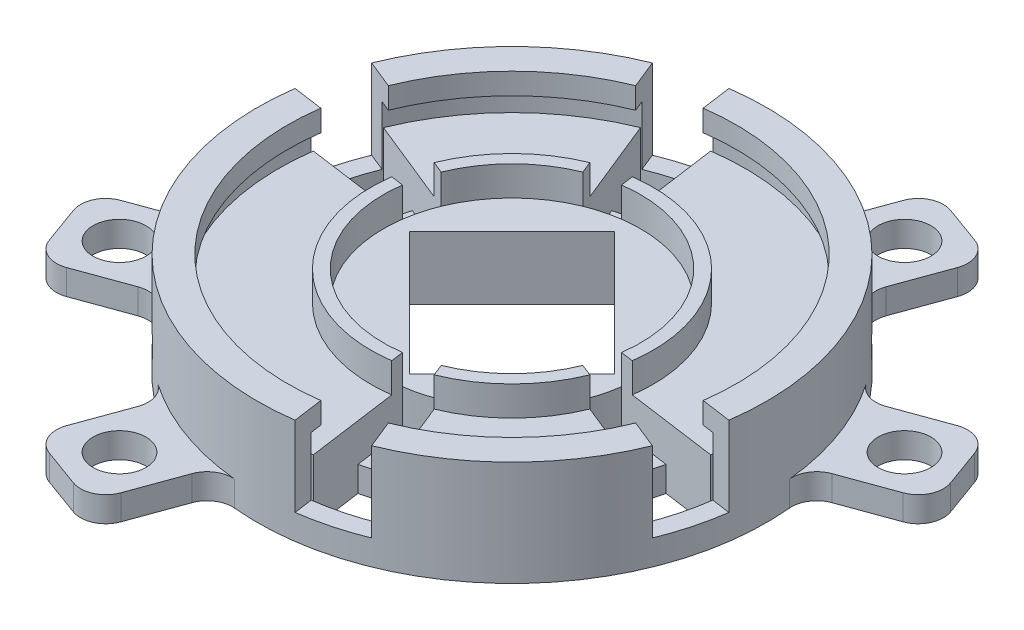
SolidWorks part; units mm, degrees
note: The reader was unsure of these and kept them because the rebuilt part matched: shared geometry of "Sketch1<4>".
other "outer_ring"
other "inner_ring" parameters "D1"=2.4937, "D6"=4.2, "D7"=4.2, "D8"=4.2, "D3"=2.6742, "D4"=3.0934, "D2"=7.9846, "D5"=6.2037
ref_plane "Front Plane" through (0, 0, 0) normal (0, 0, 1) x (1, 0, 0)
ref_plane "Top Plane" through (0, 0, 0) normal (0, 1, 0) x (1, 0, 0)
ref_plane "Right Plane" through (0, 0, 0) normal (1, 0, 0) x (0, 0, -1)
sketch "Sketch1" plane through (0, 0, 0) normal (0, 0, 1) x (1, 0, 0)
  line L4 (17.5401, 1.65) -> (17.5401, 3.34)
  line L5 (17.5401, 3.34) -> (19.9401, 3.34)
  line L6 (19.9401, 3.34) -> (19.9401, -5)
  line L7 (19.9401, -5) -> (-0.2599, -5)
  line L9 (10.9401, 0) -> (18.4401, 0)
  line L10 (16.9401, 3.15) -> (16.9401, 1.55) construction
  line L11 (10.9401, 0) -> (10.9401, 2.35)
  line L15 (-0.2599, 0) -> (-0.2599, -5)
  line L16 (18.2401, 0) -> (18.2401, 1.55) construction
  line L18 (9.9401, 2.35) -> (9.9401, 0)
  line L19 (18.4401, 0) -> (18.4401, 1.65)
  line L20 (9.9401, 0) -> (-0.2599, 0)
  line L21 (-18.7599, 1.55) -> (18.2401, 1.55) construction
  line L22 (-0.2599, -998.45) -> (-0.2599, 49001.55) construction
  line L23 (10.9401, -4) -> (10.9401, 0)
  line L24 (10.9401, -4) -> (-0.2599, -4)
  line L25 (18.4401, 0) -> (18.4401, -5)
  line L27 (10.9401, 2.35) -> (9.9401, 2.35)
  line L28 (9.2788, 3.15) -> (9.2788, 1.55) construction
  line L30 (18.4401, 1.65) -> (17.5401, 1.65)
  line L31 (18.2401, -5) -> (18.2401, 0)
  line L32 (-18.7599, 0) -> (18.2401, 0) construction
  line L33 (11.0901, 0) -> (11.0901, 1.55) construction
  point P24 (9.2788, 2.35)
  point P28 (-0.2599, 1.55)
  dimension "D1" = 5
  dimension "D2" = 0.6
  dimension "D3" = 1.69
  dimension "D4" = 0.2
  dimension "D5" = 1
  dimension "D6" = 0.1
  dimension "D7" = 0.7
  dimension "D8" = 4
  dimension "D9" = 1.5
  dimension "D10" = 0.15
revolve "Revolve1" add sketch "Sketch1" angle 360 about L22
revolve "Revolve3" add sketch "Sketch1<4>" angle 360 about L22
sketch "Sketch1<4>" plane through (0, 0, 0) normal (0, 0, 1) x (1, 0, 0) same geometry as "Sketch1"
sketch "Sketch4" plane through (0, -5, 0) normal (0, -1, 0) x (1, 0, 0)
  circle A0 centre (-7.3664, -7.7428) radius 1.6
  circle A1 centre (7.4829, 7.1064) radius 1.6
  dimension "D1" = 3.2
extrude "Cut-Extrude1" cut sketch "Sketch4" against normal blind 4
sketch "Sketch5" plane through (0, -5, 0) normal (0, -1, 0) x (1, 0, 0)
  line L0 (3.8236, -13.877) -> (-9.2225, -0.8309)
  line L1 (3.8236, -13.877) -> (13.617, -4.0835)
  line L2 (-9.2225, -0.8309) -> (0.5709, 8.9626)
  line L3 (13.617, -4.0835) -> (0.5709, 8.9626)
  line L6 (-6.2704, 0) -> (-0.2599, 6.0104) construction
  line L7 (3.1165, -11.0485) -> (1.773, -9.705) construction
  line L8 (9.3744, -6.2049) -> (4.5307, -11.0485) construction
  line L10 (-3.2652, 3.0052) -> (-4.3258, 4.0659) construction
  dimension "D1" = 1.5
  dimension "D2" = 1.5
  dimension "D4" = 1.5
extrude "Cut-Extrude2" cut sketch "Sketch5" against normal blind 2.5
sketch "Sketch6" plane through (0, -2.5, 0) normal (0, -1, 0) x (1, 0, 0)
  line L0 (-9.2225, -0.8309) -> (0.5709, 8.9626)
  line L1 (-9.2225, -0.8309) -> (-1.0908, -8.9626)
  line L2 (0.5709, 8.9626) -> (8.7026, 0.8309)
  line L3 (-1.0908, -8.9626) -> (8.7026, 0.8309)
  line L4 (0.3234, -5.427) -> (5.1671, -0.5834) construction
  line L6 (-9.2225, -0.8309) -> (3.8236, -13.877) construction
  dimension "D1" = 1.5
extrude "Cut-Extrude3" cut sketch "Sketch6" against normal through all
sketch "Sketch10" plane through (0, 3.34, 0) normal (0, 1, 0) x (1, 0, 0)
  line L0 (-3.0515, 20.0062) -> (-1.6695, 10.1021)
  line L1 (-4.0903, 9.4535) -> (-7.8455, 18.7216)
  line L2 (-1.5659, 20.2135) -> (-4.5371, 19.7989) construction
  line L3 (-9.2357, 18.1584) -> (-6.4553, 19.2849) construction
  circle A0 centre (-0.2599, 0) radius 20.2 construction
  circle A1 centre (-0.2599, 0) radius 10.2
  arc A2 (-1.6695, 10.1021) -> (-4.0903, 9.4535) centre (-0.2599, 0) ccw
  arc A3 (-3.0515, 20.0062) -> (-7.8455, 18.7216) centre (-0.2599, 0) ccw
  circle A4 centre (-0.2599, 0) radius 10.2 construction
  point P12 (-3.0515, 20.0062)
  point P16 (-7.8455, 18.7216)
  dimension "D2" = 3
  dimension "D1" = 0
extrude "Cut-Extrude6" cut sketch "Sketch10" against normal offset from surface (6.34 mm away) 2 up to face at (-0.2599, -5, -18.7)
sketch "Sketch16" plane through (0, -3, 0) normal (0, 1, 0) x (1, 0, 0)
  line L0 (-5.6487, 13.2998) -> (-2.2431, 14.2123)
  line L1 (-2.8166, 18.3225) -> (-1.6695, 10.1021) construction
  line L2 (-7.2071, 17.1461) -> (-4.0903, 9.4535)
  line L3 (-1.6695, 10.1021) -> (-2.8166, 18.3225)
  line L4 (-7.2071, 17.1461) -> (-5.6487, 13.2998)
  line L5 (-2.2431, 14.2123) -> (-2.8166, 18.3225)
  line L6 (-4.0903, 9.4535) -> (-7.2071, 17.1461) construction
  arc A2 (-1.6695, 10.1021) -> (-4.0903, 9.4535) centre (-0.2599, 0) ccw
  arc A3 (-2.8166, 18.3225) -> (-7.2071, 17.1461) centre (-0.2599, 0) ccw
  arc A5 (-2.8166, 18.3225) -> (-7.2071, 17.1461) centre (-0.2599, 0) ccw
  dimension "D1" = 0
extrude "Cut-Extrude11" cut sketch "Sketch16" against normal through all
pattern_circular "CirPattern2" count 12 over 360 about axis through (-0.2599, -998.45, 0) along (0, -1, 0) skipping 1, 2, 3, 5, 7, 8, 9, 11 of "Cut-Extrude6", "Cut-Extrude11"
ref_plane "Plane6" through (-0.13, 0, 0.13) normal (-0.7071, 0, 0.7071) x (0.7071, 0, 0.7071)
ref_plane "Plane7" through (-0.13, 0, -0.13) normal (0.7071, 0, 0.7071) x (0.7071, 0, -0.7071)
ref_plane "Plane8" through (14.1536, 0, -14.1536) normal (0.7071, 0, -0.7071) x (-0.7071, 0, -0.7071)
sketch "Sketch13" plane through (14.1536, 0, -14.1536) normal (0.7071, 0, -0.7071) x (-0.7071, 0, -0.7071)
  line L0 (-18.3162, -5) -> (18.6838, -5) construction
  line L1 (0.1838, -5) -> (0.1838, 0) construction
  line L3 (14.9476, 0) -> (-14.58, 0) construction
  circle A0 centre (0.1838, -2.5) radius 1.6
  point P12 (0.1838, -2.5)
  dimension "D1" = 3.2
extrude "Cut-Extrude7" cut sketch "Sketch13" against normal blind 4.5
sketch "Sketch14" plane through (14.1536, 0, -14.1536) normal (0.7071, 0, -0.7071) x (-0.7071, 0, -0.7071)
  circle A0 centre (0.1838, -2.5) radius 1.15
  circle A2 centre (0.1838, -2.5) radius 1.6 construction
  dimension "D1" = 2.3
extrude "Cut-Extrude10" cut sketch "Sketch14" along normal through all both and the other way through all
mirror "Mirror1" about plane through (-0.13, 0, 0.13) normal (-0.7071, 0, 0.7071) of "Cut-Extrude7"
sketch "Sketch15" plane through (0, -5, 0) normal (0, -1, 0) x (1, 0, 0)
  line L4 (-0.2599, 0) -> (35355.0791, -35355.3391) construction
  line L5 (17.5945, -3.0052) -> (2.7453, -17.8544) construction
  line L10 (16.081, -9.7787) -> (18.5436, -3.0129)
  line L11 (16.081, -9.7787) -> (24.7262, -12.9253)
  line L12 (18.5436, -3.0129) -> (27.1887, -6.1595)
  line L13 (24.7262, -12.9253) -> (27.1887, -6.1595)
  line L14 (-0.2599, 0) -> (25.9575, -9.5424) construction
  line L15 (-0.2599, 0) -> (9.2824, -26.2174) construction
  line L16 (12.6653, -24.9862) -> (5.8995, -27.4487)
  line L17 (2.7529, -18.8035) -> (5.8995, -27.4487)
  line L18 (9.5187, -16.341) -> (12.6653, -24.9862)
  line L19 (9.5187, -16.341) -> (2.7529, -18.8035)
  line L20 (-0.2599, 0) -> (35355.0791, 35355.3391) construction
  line L21 (-0.2599, 0) -> (-26.4774, 9.5424) construction
  line L22 (-0.2599, 0) -> (-9.8023, 26.2174) construction
  line L23 (-16.6009, 9.7787) -> (-19.0635, 3.0129)
  line L24 (-16.6009, 9.7787) -> (-25.2461, 12.9253)
  line L25 (-19.0635, 3.0129) -> (-27.7086, 6.1595)
  line L26 (-25.2461, 12.9253) -> (-27.7086, 6.1595)
  line L27 (-13.1852, 24.9862) -> (-6.4194, 27.4487)
  line L28 (-3.2728, 18.8035) -> (-6.4194, 27.4487)
  line L29 (-10.0386, 16.341) -> (-13.1852, 24.9862)
  line L30 (-10.0386, 16.341) -> (-3.2728, 18.8035)
  circle A0 centre (-0.2599, 0) radius 18.7 construction
  circle A3 centre (22.5746, -8.3111) radius 2.1
  circle A4 centre (8.0511, -22.8345) radius 2.1
  circle A5 centre (-0.2599, 0) radius 20.2 construction
  circle A6 centre (-23.0945, 8.3111) radius 2.1
  circle A7 centre (-8.571, 22.8345) radius 2.1
  point P9 (10.1699, -10.4298)
  point P15 (17.3123, -6.3958)
  point P17 (25.9575, -9.5424)
  dimension "D4" = 4.2
  dimension "D1" = 1.5
  dimension "D2" = 1.5
  dimension "D3" = 2
  dimension "D5" = 50
extrude "Boss-Extrude1" add sketch "Sketch15" against normal blind 2
fillet "Fillet1" radius 2 16 edges at (19.6492, -4, -3.4153) (9.9211, -4, -17.4466) (3.1554, -4, -19.9092) (17.1867, -4, -10.1811) (5.8995, -4, -27.4487) (12.6653, -4, -24.9862) (27.1887, -4, -6.1595) (24.7262, -4, -12.9253) (-3.6753, -4, 19.9092) (-6.4194, -4, 27.4487) (-13.1852, -4, 24.9862) (-10.441, -4, 17.4466) (-17.7066, -4, 10.1811) (-20.1691, -4, 3.4153) (-25.2461, -4, 12.9253) (-27.7086, -4, 6.1595)
equation "\"width\"= 24"
equation "\"thk\"= 3"
equation "\"holesize\"= 4.2"
equation "\"holedistance\"= ( 20 + 12 ) / 2"
equation "\"threaded_hole\"= 3.9"
equation "\"fillet_radius\"= 2"
equation "\"ground_clearance\"= 25"
equation "\"tire_thk\"= 3"
equation "\"innerwheel_diam\" = \"wheel_diam\"-2*\"tire_thk\""
equation "\"innerwheel_thk\"= 8"
equation "\"wheel_diam\"= 2*(\"width\"/2+\"ground_clearance\")"
equation "\"coloursensor_holesize\"= 2.65"
equation "\"hole_to_edge\" = 4"
equation "\"M4_insert_diam\"= 5.7"
equation "\"D4@Sketch15\"=\"holesize\""
